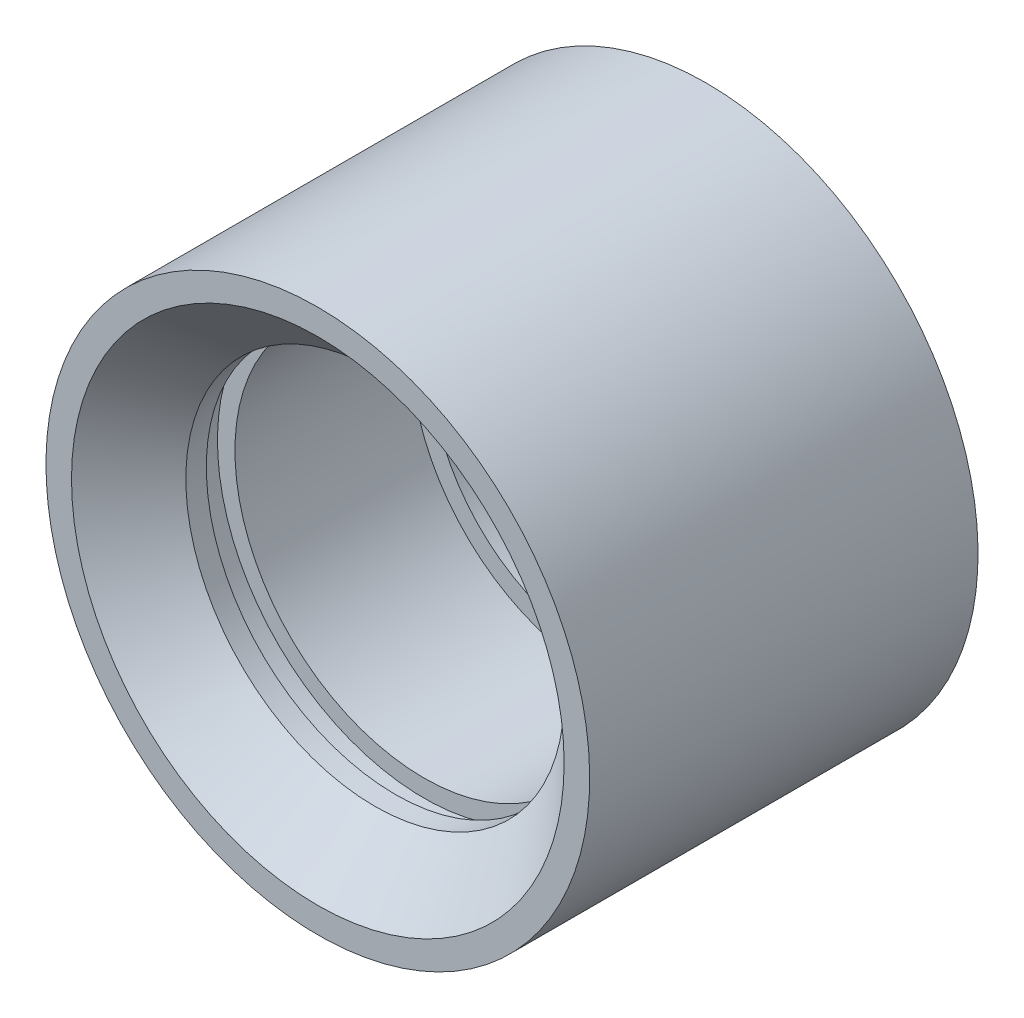
SolidWorks part; units mm, degrees
material "AISI 4130 Steel, normalized at 870C"
ref_plane "Top" through (0, 0, 0) normal (0, 0, 1) x (1, 0, 0)
ref_plane "Right" through (0, 0, 0) normal (0, 1, 0) x (1, 0, 0)
ref_plane "Front" through (0, 0, 0) normal (1, 0, 0) x (0, 0, -1)
sketch "Sketch1" plane through (0, 0, 0) normal (1, 0, 0) x (0, 0, -1)
  line L0 (7.9375, 0) -> (-7.9375, 0) construction
  line L1 (4.8146, 6.9456) -> (7.9375, 10.0686) construction
  line L2 (-7.9375, -10.0686) -> (7.9375, -10.0686)
  line L3 (4.8146, 6.9456) -> (3.5941, 6.9456) construction
  line L4 (3.5941, -6.9456) -> (4.8146, -6.9456)
  line L5 (-4.7625, -7.7318) -> (-5.6007, -7.7318)
  line L6 (-4.7625, -7.7318) -> (-4.7625, -8.4455)
  line L7 (-4.7625, -8.4455) -> (-3.5941, -8.4455)
  line L8 (-3.5941, -8.4455) -> (-3.5941, -7.7318)
  line L9 (-3.5941, -7.7318) -> (3.5941, -7.7318)
  line L10 (3.5941, -7.7318) -> (3.5941, -6.9456)
  line L11 (3.5941, 7.7318) -> (3.5941, 6.9456) construction
  line L12 (-3.5941, 7.7318) -> (3.5941, 7.7318) construction
  line L13 (-3.5941, 8.4455) -> (-3.5941, 7.7318) construction
  line L14 (-4.7625, 8.4455) -> (-3.5941, 8.4455) construction
  line L15 (-4.7625, 7.7318) -> (-4.7625, 8.4455) construction
  line L16 (-4.7625, 7.7318) -> (-5.6007, 7.7318)
  line L17 (-5.6007, 7.7318) -> (-7.9375, 10.0686)
  line L19 (-7.9375, 10.0686) -> (7.9375, 10.0686) construction
  line L21 (0, 10.0686) -> (0, -10.0686) construction
  line L22 (4.8146, -6.9456) -> (7.9375, -10.0686)
  line L23 (-5.6007, -7.7318) -> (-7.9375, -10.0686)
  line L24 (7.9375, -10.0686) -> (7.9375, -11.1125)
  line L25 (7.9375, -11.1125) -> (-7.9375, -11.1125)
  line L26 (-7.9375, -11.1125) -> (-7.9375, -10.0686)
  line L27 (-7.9375, 11.1125) -> (-7.9375, 10.0686) construction
  line L28 (7.9375, 11.1125) -> (-7.9375, 11.1125) construction
  line L29 (7.9375, 10.0686) -> (7.9375, 11.1125) construction
  point P24 (0, -7.7318)
  point P33 (0, 0)
  dimension "D1" = 15.875
  dimension "D2" = 15.4635
  dimension "D3" = 16.891
  dimension "D4" = 45
  dimension "D5" = 45
  dimension "D6" = 1.6231
  dimension "D7" = 1.1684
  dimension "D8" = 7.1882
  dimension "D9" = 1.2205
  dimension "D10" = 13.8913
  dimension "D13" = 0.7137
  dimension "D14" = 22.225
revolve "Body" add sketch "Sketch1" angle 360 about L0 region at (0, -8.9271, -0.2833) region at (0, -10.5905, 0)
ref_axis "Center Axis" through (0, 0, 3.5941) along (0, 0, -1)
move or copy body "Body-Move/Copy5" [suppressed] bodies to move or copy 102
move or copy body "Body-Move/Copy3" [suppressed] bodies to move or copy 102
move or copy body "Body-Move/Copy4" [suppressed] bodies to move or copy 102
move or copy body "Body-Move/Copy1" [suppressed] bodies to move or copy 102
move or copy body "Body-Move/Copy2" [suppressed] bodies to move or copy 102
